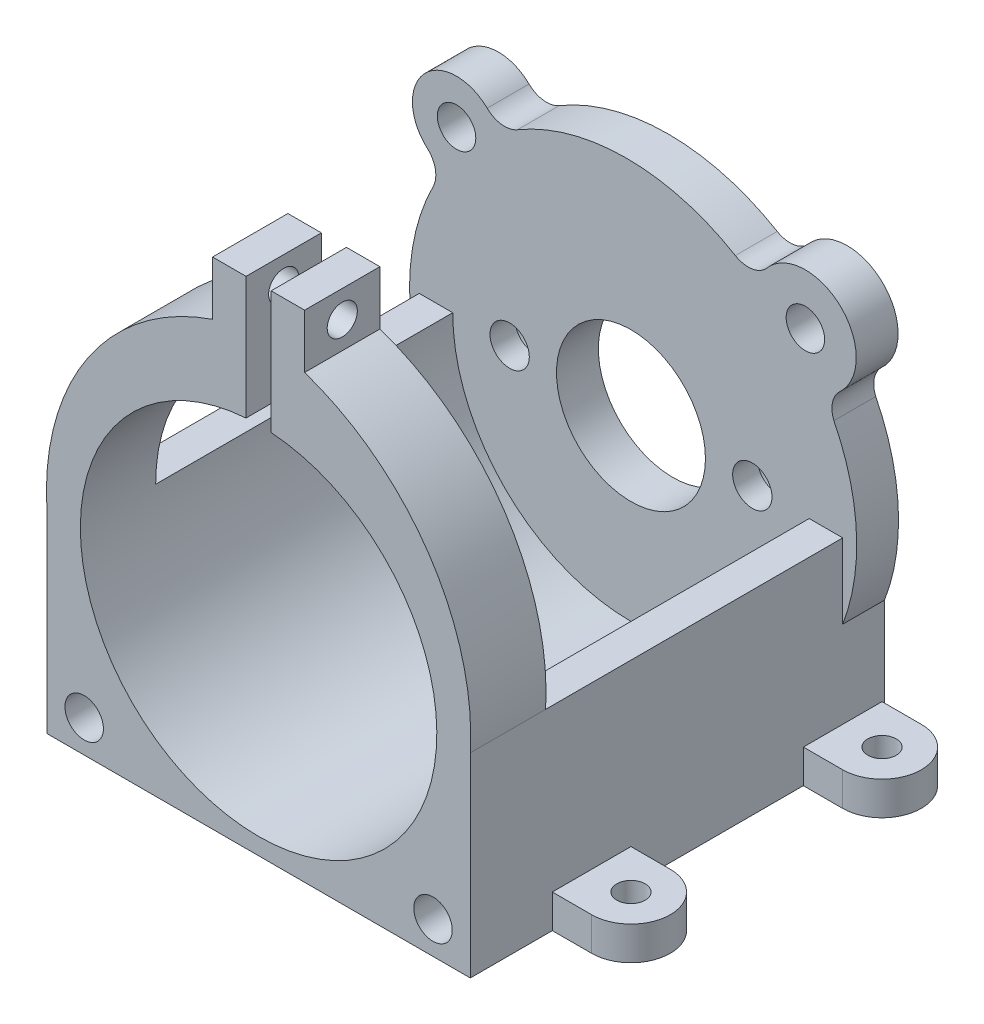
SolidWorks part; units mm, degrees
ref_plane "Спереди" through (0, 0, 0) normal (0, 0, 1) x (1, 0, 0)
ref_plane "Сверху" through (0, 0, 0) normal (0, 1, 0) x (1, 0, 0)
ref_plane "Справа" through (0, 0, 0) normal (1, 0, 0) x (0, 0, -1)
sketch "Эскиз1" plane through (0, 0, 0) normal (0, 0, 1) x (1, 0, 0)
  line L0 (0, 0) -> (-14.5, 0) construction
  line L1 (0, 0) -> (14.5, 0) construction
  line L2 (0, 0) -> (0, 14.5) construction
  line L3 (0, 0) -> (0, -14.5) construction
  line L5 (20.8436, -19.437) -> (-20.8436, -19.437) construction
  line L6 (20.8436, -19.437) -> (20.8436, 19.437) construction
  line L7 (20.8436, 19.437) -> (-20.8436, 19.437) construction
  line L8 (-20.8436, -19.437) -> (-20.8436, 19.437) construction
  line L9 (20.8436, -19.437) -> (-20.8436, 19.437) construction
  line L10 (20.8436, 19.437) -> (-20.8436, -19.437) construction
  circle A1 centre (-14.5, 0) radius 2.35
  circle A2 centre (14.5, 0) radius 2.35
  circle A3 centre (0, 0) radius 8.9
  circle A4 centre (0, 14.5) radius 1.75 construction
  circle A5 centre (0, -14.5) radius 1.75 construction
  arc A70 (-13.7505, -22.6081) -> (-17.3677, -23.0311) centre (-15.2821, -25.1876) ccw
  arc A71 (-13.7505, -22.6081) -> (12.2878, -22.6081) centre (-0.7314, -0.682) ccw
  arc A72 (15.905, -23.0311) -> (12.2878, -22.6081) centre (13.8194, -25.1876) ccw
  arc A73 (15.905, -23.0311) -> (24.9273, -14.8948) centre (20.8436, -19.437) ccw
  arc A74 (24.253, -11.3159) -> (24.9273, -14.8948) centre (26.9331, -12.6639) ccw
  arc A75 (24.253, -11.3159) -> (24.253, 11.5999) centre (1.4722, 0.142) ccw
  arc A76 (24.9061, 14.9185) -> (24.253, 11.5999) centre (27.0108, 12.7807) ccw
  arc A77 (24.9061, 14.9185) -> (16.0938, 23.2264) centre (20.8436, 19.437) ccw
  arc A78 (12.4766, 22.8033) -> (16.0938, 23.2264) centre (14.0083, 25.3829) ccw
  arc A79 (12.4766, 22.8033) -> (-13.5616, 22.8033) centre (-0.5425, 0.8773) ccw
  arc A80 (-17.1788, 23.2264) -> (-13.5616, 22.8033) centre (-15.0933, 25.3829) ccw
  arc A81 (-17.1788, 23.2264) -> (-24.314, 15.4687) centre (-20.8436, 19.437) ccw
  arc A82 (-23.6396, 11.8898) -> (-24.314, 15.4687) centre (-26.3197, 13.2378) ccw
  arc A83 (-23.6396, 11.8898) -> (-23.5122, -12.1399) centre (0, 0) ccw
  arc A84 (-24.1865, -15.7188) -> (-23.5122, -12.1399) centre (-26.1923, -13.4879) ccw
  arc A85 (-24.1865, -15.7188) -> (-17.3677, -23.0311) centre (-20.8436, -19.437) ccw
  dimension "D2" = 4.7
  dimension "D3" = 14.5
  dimension "D4" = 17.8
  dimension "D5" = 3.5
  dimension "D1" = 14.5
  dimension "D6" = 57
extrude "Бобышка-Вытянуть1" add sketch "Эскиз1" along normal blind 5
sketch "Эскиз2" plane through (0, 0, 5) normal (0, 0, 1) x (1, 0, 0)
  line L0 (-25.3, 0) -> (-21.3, 0)
  line L1 (21.3, 0) -> (25.3, 0)
  line L2 (0, -28.25) -> (0, -23.25) construction
  line L3 (0, -23.25) -> (16.0468, -23.25) construction
  line L4 (35.3, -23.25) -> (50, -23.25)
  line L5 (-35.3, -23.25) -> (-50, -23.25)
  line L6 (-25.3, 0) -> (-25.3, -13.25)
  line L7 (25.3, 0) -> (25.3, -13.25)
  line L8 (-50, -23.25) -> (-50, -28.25)
  line L9 (-50, -28.25) -> (50, -28.25)
  line L10 (50, -28.25) -> (50, -23.25)
  arc A0 (-21.3, 0) -> (21.3, 0) centre (0, 0) ccw
  arc A2 (35.3, -23.25) -> (25.3, -13.25) centre (35.3, -13.25) cw
  arc A3 (-25.3, -13.25) -> (-35.3, -23.25) centre (-35.3, -13.25) cw
  dimension "D1" = 10
  dimension "D6" = 21.3
  dimension "D2" = 5
  dimension "D3" = 100
  dimension "D4" = 5
  dimension "D5" = 4
extrude "Бобышка-Вытянуть2" add sketch "Эскиз2" along normal blind 44.5 and the other way blind 5
sketch "Эскиз4" plane through (0, 0, 49.5) normal (0, 0, 1) x (1, 0, 0)
  line L0 (0, 0) -> (0, 30) construction
  line L1 (21.3, 0) -> (25.3, 0)
  line L2 (-25.3, 0) -> (-21.3, 0)
  line L3 (0, 30) -> (-1.5, 30) construction
  line L4 (0, 30) -> (1.5, 30) construction
  line L5 (-1.5, 29.9162) -> (-1.5, 21.2471)
  line L6 (1.5, 29.9162) -> (1.5, 21.2471)
  line L7 (-1.5, 29.9162) -> (-1.5, 35.9162)
  line L8 (-1.5, 35.9162) -> (-5.5, 35.9162)
  line L9 (-5.5, 35.9162) -> (-5.5, 29.4654)
  line L10 (1.5, 29.9162) -> (1.5, 35.9162)
  line L11 (1.5, 35.9162) -> (5.5, 35.9162)
  line L12 (5.5, 35.9162) -> (5.5, 29.4654)
  arc A0 (21.3, 0) -> (1.5, 21.2471) centre (0, 0) ccw
  arc A1 (-5.5, 29.4654) -> (-25.3, 0) centre (3.9362, 1.7393) ccw
  arc A2 (5.5, 29.4654) -> (25.3, 0) centre (-3.9362, 1.7393) cw
  arc A3 (-1.5, 21.2471) -> (-21.3, 0) centre (0, 0) ccw
  dimension "D1" = 30
  dimension "D2" = 1.5
  dimension "D3" = 6
  dimension "D4" = 4
extrude "Бобышка-Вытянуть3" add sketch "Эскиз4" against normal blind 9
sketch "Эскиз5" plane through (-5.5, 0, 0) normal (-1, 0, 0) x (0, 0, 1)
  line L0 (45, 35.9162) -> (45, 29.4654) construction
  line L1 (40.5, 35.9162) -> (49.5, 35.9162) construction
  line L2 (40.5, 29.4654) -> (49.5, 29.4654) construction
  circle A0 centre (45, 32.6908) radius 1.8
  dimension "D1" = 3.6
extrude "Вырез-Вытянуть2" cut sketch "Эскиз5" against normal blind 19
sketch "Эскиз9" plane through (0, -23.25, 0) normal (0, 1, 0) x (1, 0, 0)
  line L0 (25.3, 0) -> (25.3, -49.5)
  line L1 (-25.3, 0) -> (25.3, 0)
  line L2 (-25.3, 0) -> (-25.3, -49.5)
  line L3 (-25.3, -49.5) -> (25.3, -49.5)
  line L5 (-59.8904, -57.7314) -> (58.8188, -57.7314)
  line L6 (-59.8904, -57.7314) -> (-59.8904, 10.3746)
  line L7 (-59.8904, 10.3746) -> (58.8188, 10.3746)
  line L8 (58.8188, -57.7314) -> (58.8188, 10.3746)
  line L9 (25.3, -49.5) -> (35.3, -49.5) construction
extrude "Вырез-Вытянуть5" cut sketch "Эскиз9" against normal blind 10 and the other way blind 10
sketch "Эскиз10" plane through (0, 0, 49.5) normal (0, 0, 1) x (1, 0, 0)
  line L0 (0, -21.3) -> (0, -23.3) construction
  line L1 (-25.3, -28.25) -> (-25.3, -23.3)
  line L2 (-25.3, 0) -> (-25.3, -28.25) construction
  line L3 (-25.3, -23.3) -> (25.3, -23.3)
  line L4 (25.3, -28.25) -> (25.3, 0) construction
  line L5 (25.3, -23.3) -> (25.3, -28.25)
  line L6 (25.3, -28.25) -> (-25.3, -28.25)
  arc A0 (-1.5, 21.2471) -> (1.5, 21.2471) centre (0, 0) ccw construction
  dimension "D1" = 2
extrude "Вырез-Вытянуть6" cut sketch "Эскиз10" against normal through all
sketch "Эскиз11" plane through (0, 0, 0) normal (0, 0, -1) x (-1, 0, 0)
  line L1 (-20.8436, 19.437) -> (20.8436, 19.437) construction
  line L2 (-20.8436, 19.437) -> (-20.8436, -19.437) construction
  line L3 (-20.8436, -19.437) -> (20.8436, -19.437) construction
  line L4 (20.8436, 19.437) -> (20.8436, -19.437) construction
  line L5 (-20.8436, 19.437) -> (20.8436, -19.437) construction
  line L6 (-20.8436, -19.437) -> (20.8436, 19.437) construction
  circle A1 centre (-20.8436, -19.437) radius 2.3
  circle A2 centre (20.8436, -19.437) radius 2.3
  point P0 (0, 0)
  dimension "D1" = 4.6
  dimension "D2" = 57
extrude "Вырез-Вытянуть7" cut sketch "Эскиз11" against normal through all
sketch "Эскиз12" plane through (0, 0, 0) normal (0, 0, -1) x (-1, 0, 0)
  line L1 (20.8436, -19.437) -> (-20.8436, -19.437) construction
  line L2 (20.8436, -19.437) -> (20.8436, 19.437) construction
  line L3 (20.8436, 19.437) -> (-20.8436, 19.437) construction
  line L4 (-20.8436, -19.437) -> (-20.8436, 19.437) construction
  line L5 (20.8436, -19.437) -> (-20.8436, 19.437) construction
  line L6 (20.8436, 19.437) -> (-20.8436, -19.437) construction
  circle A0 centre (-20.8436, 19.437) radius 2.3
  circle A1 centre (20.8436, 19.437) radius 2.3
  point P2 (0, 0)
  dimension "D1" = 4.6
  dimension "D2" = 57
extrude "Вырез-Вытянуть8" cut sketch "Эскиз12" against normal blind 10
sketch "Эскиз13" plane through (0, 0, 0) normal (0, 0, -1) x (-1, 0, 0)
  circle A0 centre (-14.5, 0) radius 4.5
  circle A1 centre (14.5, 0) radius 4.5
  dimension "D1" = 9
extrude "Вырез-Вытянуть9" cut sketch "Эскиз13" against normal blind 2
sketch "Эскиз14" plane through (0, -23.3, 0) normal (0, -1, 0) x (1, 0, 0)
  line L0 (0, 0) -> (0, 35) construction
  line L1 (0, 35) -> (-30, 35) construction
  line L2 (-30, 39.7) -> (-25.3, 39.7)
  line L3 (-25.3, 0) -> (-25.3, 49.5) construction
  line L4 (-30, 30.3) -> (-25.3, 30.3)
  line L5 (-25.3, 39.7) -> (-25.3, 30.3)
  line L6 (25.3, 39.7) -> (25.3, 30.3)
  line L7 (30, 30.3) -> (25.3, 30.3)
  line L8 (30, 39.7) -> (25.3, 39.7)
  line L9 (0, 20) -> (-25.3, 20) construction
  line L10 (30, 0.3) -> (25.3, 0.3)
  line L11 (30, 9.7) -> (25.3, 9.7)
  line L12 (25.3, 0.3) -> (25.3, 9.7)
  line L13 (-25.3, 0.3) -> (-25.3, 9.7)
  line L14 (-30, 9.7) -> (-25.3, 9.7)
  line L15 (-30, 0.3) -> (-25.3, 0.3)
  line L17 (25.3, 0) -> (-25.3, 0) construction
  circle A0 centre (-30, 35) radius 1.7
  arc A1 (-30, 39.7) -> (-30, 30.3) centre (-30, 35) ccw
  arc A2 (30, 39.7) -> (30, 30.3) centre (30, 35) cw
  circle A3 centre (30, 35) radius 1.7
  circle A4 centre (30, 5) radius 1.7
  arc A5 (30, 0.3) -> (30, 9.7) centre (30, 5) ccw
  arc A6 (-30, 0.3) -> (-30, 9.7) centre (-30, 5) cw
  circle A7 centre (-30, 5) radius 1.7
  dimension "D1" = 3.4
  dimension "D2" = 3
  dimension "D3" = 35
  dimension "D4" = 30
  dimension "D5" = 20
extrude "Бобышка-Вытянуть4" add sketch "Эскиз14" against normal blind 4
